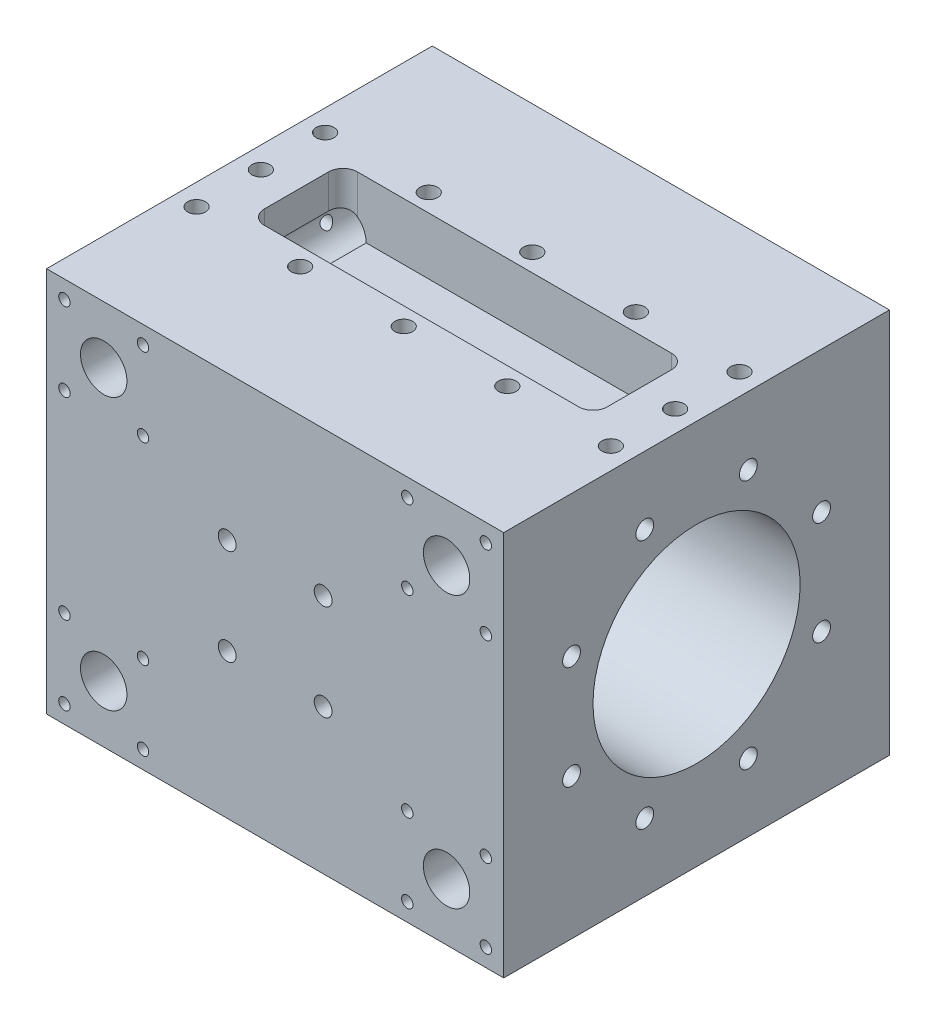
SolidWorks part; units mm, degrees
material "AISI 1020"
ref_plane "Front Plane" through (0, 0, 0) normal (0, 0, 1) x (1, 0, 0)
ref_plane "Top Plane" through (0, 0, 0) normal (0, 1, 0) x (1, 0, 0)
ref_plane "Right Plane" through (0, 0, 0) normal (1, 0, 0) x (0, 0, -1)
sketch "Sketch1" plane through (0, 0, 0) normal (0, 1, 0) x (1, 0, 0)
  line L1 (-32, -27) -> (32, -27)
  line L2 (-32, -27) -> (-32, 27)
  line L3 (-32, 27) -> (32, 27)
  line L4 (32, -27) -> (32, 27)
  line L5 (-32, -27) -> (32, 27) construction
  line L6 (-32, 27) -> (32, -27) construction
  point P0 (0, 0)
  dimension "D1" = 27
  dimension "D2" = 32
extrude "Boss-Extrude1" add sketch "Sketch1" along normal mid plane 54
sketch "Sketch2" plane through (0, 27, 0) normal (0, 1, 0) x (1, 0, 0)
  line L1 (-22, -6.5) -> (22, -6.5)
  line L2 (-24, -4.5) -> (-24, 4.5)
  line L3 (-22, 6.5) -> (22, 6.5)
  line L4 (24, -4.5) -> (24, 4.5)
  line L5 (-24, -6.5) -> (24, 6.5) construction
  line L6 (-24, 6.5) -> (24, -6.5) construction
  arc A0 (22, -6.5) -> (24, -4.5) centre (22, -4.5) ccw
  arc A1 (22, 6.5) -> (24, 4.5) centre (22, 4.5) cw
  arc A2 (-24, 4.5) -> (-22, 6.5) centre (-22, 4.5) cw
  arc A3 (-22, -6.5) -> (-24, -4.5) centre (-22, -4.5) cw
  point P0 (0, 0)
  dimension "D3" = 2
  dimension "D1" = 24
  dimension "D2" = 6.5
extrude "Cut-Extrude1" cut sketch "Sketch2" against normal blind 8
sketch "Sketch7" plane through (0, 27, 0) normal (0, 1, 0) x (1, 0, 0)
  point P0 (-29, 0)
  point P2 (-29, 9)
  point P4 (-29, -9)
  point P6 (-14.5, -9)
  point P8 (0, -9)
  point P10 (14.5, -9)
  point P12 (29, -9)
  point P14 (29, 0)
  point P16 (29, 9)
  point P18 (14.5, 9)
  point P20 (0, 9)
  point P22 (-14.5, 9)
  dimension "D1" = 9
  dimension "D2" = 9
  dimension "D3" = 14.5
  dimension "D4" = 14.5
  dimension "D5" = 14.5
  dimension "D6" = 14.5
hole_wizard "M3x0.5 Tapped Hole1" positions "Sketch7" profile "Sketch6" tap size "M3x0.5" standard "ANSI Metric"
sketch "Sketch6" plane through (-29, 27, 0) normal (1, 0, 0) x (0, 0, 1)
  line L0 (0, 0) -> (0, 5.5)
  line L1 (0, 5.5) -> (1.25, 4.7489)
  line L2 (1.25, 4.7489) -> (1.25, 0)
  line L5 (1.25, 0) -> (0, 0)
  line L10 (0, 5.5) -> (-1.25, 4.7489) construction
  line L11 (0, -6.35) -> (0, 107.95) construction
  dimension "Tap Drill Dia." = 2.5
  dimension "Tap Drill Depth" = 5.5
  dimension "Drill Angle" = 118
cosmetic thread "Hole Thread1" parameters "D1"=4, "D2"=3
cosmetic thread "Hole Thread2" parameters "D1"=4, "D2"=3
cosmetic thread "Hole Thread3" parameters "D1"=4, "D2"=3
cosmetic thread "Hole Thread4" parameters "D1"=4, "D2"=3
cosmetic thread "Hole Thread5" parameters "D1"=4, "D2"=3
cosmetic thread "Hole Thread6" parameters "D1"=4, "D2"=3
cosmetic thread "Hole Thread7" parameters "D1"=4, "D2"=3
cosmetic thread "Hole Thread8" parameters "D1"=4, "D2"=3
cosmetic thread "Hole Thread9" parameters "D1"=4, "D2"=3
cosmetic thread "Hole Thread10" parameters "D1"=4, "D2"=3
cosmetic thread "Hole Thread11" parameters "D1"=4, "D2"=3
cosmetic thread "Hole Thread12" parameters "D1"=4, "D2"=3
mirror "Mirror1" about plane through (0, 0, 0) normal (0, 1, 0) of "M3x0.5 Tapped Hole1", "Cut-Extrude1"
cosmetic thread "Hole Thread13" parameters "D1"=4, "D2"=3
cosmetic thread "Hole Thread14" parameters "D1"=4, "D2"=3
cosmetic thread "Hole Thread15" parameters "D1"=4, "D2"=3
cosmetic thread "Hole Thread16" parameters "D1"=4, "D2"=3
cosmetic thread "Hole Thread17" parameters "D1"=4, "D2"=3
cosmetic thread "Hole Thread18" parameters "D1"=4, "D2"=3
cosmetic thread "Hole Thread19" parameters "D1"=4, "D2"=3
cosmetic thread "Hole Thread20" parameters "D1"=4, "D2"=3
cosmetic thread "Hole Thread21" parameters "D1"=4, "D2"=3
cosmetic thread "Hole Thread22" parameters "D1"=4, "D2"=3
cosmetic thread "Hole Thread23" parameters "D1"=4, "D2"=3
cosmetic thread "Hole Thread24" parameters "D1"=4, "D2"=3
sketch "Sketch8" plane through (32, 0, 0) normal (1, 0, 0) x (0, 0, -1)
  line L0 (0, 0) -> (17.5, 7.2487) construction
  line L1 (0, 0) -> (17.5263, 0) construction
  circle A0 centre (0, 0) radius 14.5
  point P3 (17.5, 7.2487)
  point P8 (17.5, 7.2487)
  dimension "D1" = 29
  dimension "D2" = 17.5
  dimension "D3" = 22.5
hole_wizard "M3x0.5 Tapped Hole2" positions "Sketch8" profile "Sketch9" tap size "M3x0.5" standard "ANSI Metric"
sketch "Sketch9" plane through (32, 7.2487, -17.5) normal (0, 1, 0) x (0, 0, -1)
  line L0 (0, 0) -> (0, 5.5)
  line L1 (0, 5.5) -> (1.25, 4.7489)
  line L2 (1.25, 4.7489) -> (1.25, 0)
  line L5 (1.25, 0) -> (0, 0)
  line L10 (0, 5.5) -> (-1.25, 4.7489) construction
  line L11 (0, -6.35) -> (0, 107.95) construction
  dimension "Tap Drill Dia." = 2.5
  dimension "Tap Drill Depth" = 5.5
  dimension "Drill Angle" = 118
cosmetic thread "Hole Thread25" parameters "D1"=4, "D2"=3
extrude "Cut-Extrude2" cut sketch "Sketch8<2>" against normal through all
sketch "Sketch8<2>" plane through (32, 0, 0) normal (1, 0, 0) x (0, 0, -1) same geometry as "Sketch8"
pattern_circular "CirPattern1" count 8 over 360 about axis through (32, 0, 0) along (1, 0, 0) of "M3x0.5 Tapped Hole2"
cosmetic thread "Hole Thread26" parameters "D1"=4, "D2"=3
cosmetic thread "Hole Thread27" parameters "D1"=4, "D2"=3
cosmetic thread "Hole Thread28" parameters "D1"=4, "D2"=3
cosmetic thread "Hole Thread29" parameters "D1"=4, "D2"=3
cosmetic thread "Hole Thread30" parameters "D1"=4, "D2"=3
cosmetic thread "Hole Thread31" parameters "D1"=4, "D2"=3
cosmetic thread "Hole Thread32" parameters "D1"=4, "D2"=3
mirror "Mirror2" about plane through (0, 0, 0) normal (1, 0, 0) of "CirPattern1"
cosmetic thread "Hole Thread33" parameters "D1"=4, "D2"=3
cosmetic thread "Hole Thread34" parameters "D1"=4, "D2"=3
cosmetic thread "Hole Thread35" parameters "D1"=4, "D2"=3
cosmetic thread "Hole Thread36" parameters "D1"=4, "D2"=3
cosmetic thread "Hole Thread37" parameters "D1"=4, "D2"=3
cosmetic thread "Hole Thread38" parameters "D1"=4, "D2"=3
cosmetic thread "Hole Thread39" parameters "D1"=4, "D2"=3
cosmetic thread "Hole Thread40" parameters "D1"=4, "D2"=3
sketch "Sketch10" plane through (0, 0, -27) normal (0, 0, -1) x (-1, 0, 0)
  line L1 (-6.7175, -6.7175) -> (6.7175, -6.7175) construction
  line L2 (-6.7175, -6.7175) -> (-6.7175, 6.7175) construction
  line L3 (-6.7175, 6.7175) -> (6.7175, 6.7175) construction
  line L4 (6.7175, -6.7175) -> (6.7175, 6.7175) construction
  line L5 (-6.7175, -6.7175) -> (6.7175, 6.7175) construction
  line L6 (-6.7175, 6.7175) -> (6.7175, -6.7175) construction
  point P0 (0, 0)
  dimension "D1" = 9.5
sketch "Sketch14" plane through (0, 0, -27) normal (0, 0, -1) x (-1, 0, 0)
  point P0 (-6.7175, 6.7175)
  point P3 (6.7175, 6.7175)
  point P6 (6.7175, -6.7175)
  point P9 (-6.7175, -6.7175)
hole_wizard "M3x0.5 Tapped Hole3" positions "Sketch14" profile "Sketch13" tap size "M3x0.5" standard "ANSI Metric"
sketch "Sketch13" plane through (6.7175, 6.7175, -27) normal (1, 0, 0) x (0, 1, 0)
  line L0 (0, 0) -> (0, 6.5)
  line L1 (0, 6.5) -> (1.25, 5.7489)
  line L2 (1.25, 5.7489) -> (1.25, 0)
  line L5 (1.25, 0) -> (0, 0)
  line L10 (0, 6.5) -> (-1.25, 5.7489) construction
  line L11 (0, -6.35) -> (0, 107.95) construction
  dimension "Tap Drill Dia." = 2.5
  dimension "Tap Drill Depth" = 6.5
  dimension "Drill Angle" = 118
cosmetic thread "Hole Thread41" parameters "D1"=5, "D2"=3
cosmetic thread "Hole Thread42" parameters "D1"=5, "D2"=3
cosmetic thread "Hole Thread43" parameters "D1"=5, "D2"=3
cosmetic thread "Hole Thread44" parameters "D1"=5, "D2"=3
sketch "Sketch15" plane through (0, 0, -27) normal (0, 0, -1) x (-1, 0, 0)
  line L0 (-24, 19) -> (-18.5, 24.5) construction
  circle A0 centre (-24, 19) radius 3.25
  point P5 (-18.5, 24.5)
  point P8 (-18.5, 24.5)
  dimension "D3" = 6.5
  dimension "D1" = 19
  dimension "D2" = 24
  dimension "D4" = 5.5
  dimension "D5" = 5.5
hole_wizard "M2x0.4 Tapped Hole1" positions "Sketch15" profile "Sketch16" tap size "M2x0.4" standard "ANSI Metric"
sketch "Sketch16" plane through (18.5, 24.5, -27) normal (1, 0, 0) x (0, 1, 0)
  line L0 (0, 0) -> (0, 6.2)
  line L1 (0, 6.2) -> (0.8, 5.7193)
  line L2 (0.8, 5.7193) -> (0.8, 0)
  line L5 (0.8, 0) -> (0, 0)
  line L10 (0, 6.2) -> (-0.8, 5.7193) construction
  line L11 (0, -6.35) -> (0, 107.95) construction
  dimension "Tap Drill Dia." = 1.6
  dimension "Tap Drill Depth" = 6.2
  dimension "Drill Angle" = 118
cosmetic thread "Hole Thread45" parameters "D1"=5, "D2"=2
extrude "Cut-Extrude3" cut sketch "Sketch15<2>" against normal through all
sketch "Sketch15<2>" plane through (0, 0, -27) normal (0, 0, -1) x (-1, 0, 0) same geometry as "Sketch15"
pattern_linear "LPattern1" count 2 spacing 11 along (1, 0, 0) count 2 spacing 11 along (0, -1, 0) of "M2x0.4 Tapped Hole1"
cosmetic thread "Hole Thread46" parameters "D1"=5, "D2"=2
cosmetic thread "Hole Thread47" parameters "D1"=5, "D2"=2
cosmetic thread "Hole Thread48" parameters "D1"=5, "D2"=2
pattern_linear "LPattern2" count 2 spacing 48 along (-1, 0, 0) count 2 spacing 38 along (0, -1, 0) of "LPattern1", "Cut-Extrude3"
cosmetic thread "Hole Thread49" parameters "D1"=5, "D2"=2
cosmetic thread "Hole Thread50" parameters "D1"=5, "D2"=2
cosmetic thread "Hole Thread51" parameters "D1"=5, "D2"=2
cosmetic thread "Hole Thread52" parameters "D1"=5, "D2"=2
cosmetic thread "Hole Thread53" parameters "D1"=5, "D2"=2
cosmetic thread "Hole Thread54" parameters "D1"=5, "D2"=2
cosmetic thread "Hole Thread55" parameters "D1"=5, "D2"=2
cosmetic thread "Hole Thread56" parameters "D1"=5, "D2"=2
cosmetic thread "Hole Thread57" parameters "D1"=5, "D2"=2
cosmetic thread "Hole Thread58" parameters "D1"=5, "D2"=2
cosmetic thread "Hole Thread59" parameters "D1"=5, "D2"=2
cosmetic thread "Hole Thread60" parameters "D1"=5, "D2"=2
mirror "Mirror3" about plane through (0, 0, 0) normal (0, 0, 1) of "LPattern2", "LPattern1", "M2x0.4 Tapped Hole1", "M3x0.5 Tapped Hole3"
cosmetic thread "Hole Thread61" parameters "D1"=5, "D2"=2
cosmetic thread "Hole Thread62" parameters "D1"=5, "D2"=2
cosmetic thread "Hole Thread63" parameters "D1"=5, "D2"=2
cosmetic thread "Hole Thread64" parameters "D1"=5, "D2"=2
cosmetic thread "Hole Thread65" parameters "D1"=5, "D2"=2
cosmetic thread "Hole Thread66" parameters "D1"=5, "D2"=2
cosmetic thread "Hole Thread67" parameters "D1"=5, "D2"=2
cosmetic thread "Hole Thread68" parameters "D1"=5, "D2"=2
cosmetic thread "Hole Thread69" parameters "D1"=5, "D2"=2
cosmetic thread "Hole Thread70" parameters "D1"=5, "D2"=2
cosmetic thread "Hole Thread71" parameters "D1"=5, "D2"=3
cosmetic thread "Hole Thread72" parameters "D1"=5, "D2"=2
cosmetic thread "Hole Thread73" parameters "D1"=5, "D2"=2
cosmetic thread "Hole Thread74" parameters "D1"=5, "D2"=3
cosmetic thread "Hole Thread75" parameters "D1"=5, "D2"=2
cosmetic thread "Hole Thread76" parameters "D1"=5, "D2"=2
cosmetic thread "Hole Thread77" parameters "D1"=5, "D2"=2
cosmetic thread "Hole Thread78" parameters "D1"=5, "D2"=3
cosmetic thread "Hole Thread79" parameters "D1"=5, "D2"=3
cosmetic thread "Hole Thread80" parameters "D1"=5, "D2"=2
